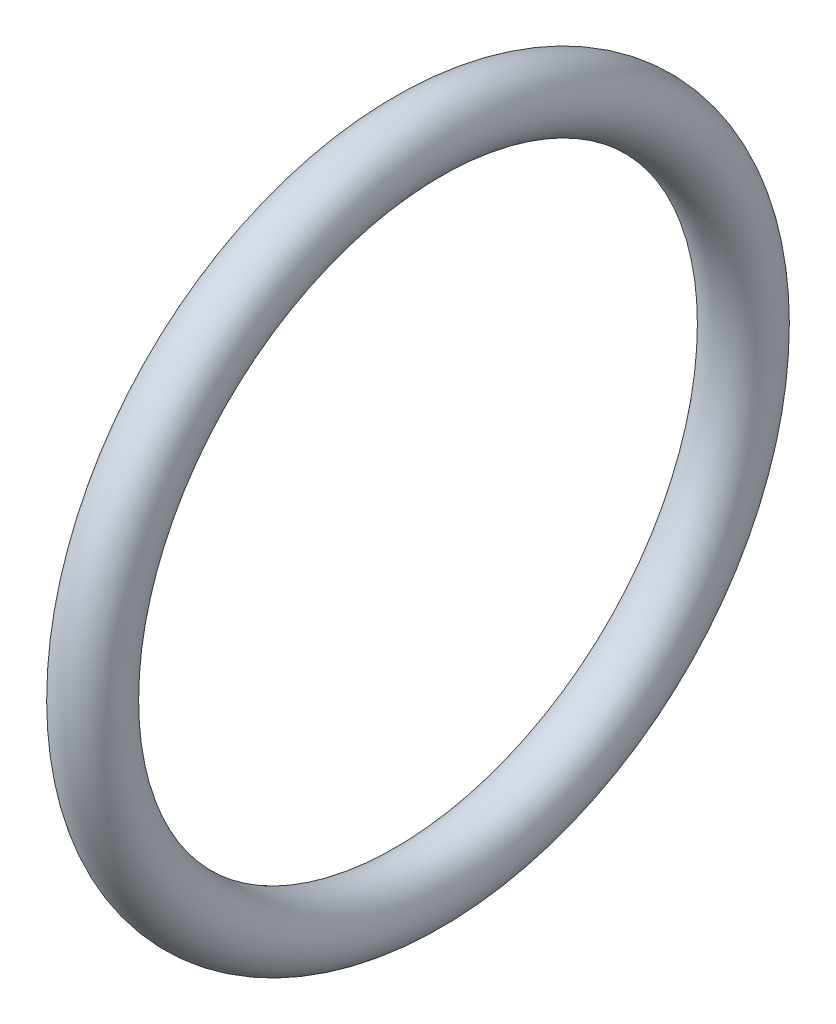
SolidWorks part; units mm, degrees
ref_plane "Plano frontal" through (0, 0, 0) normal (0, 0, 1) x (1, 0, 0)
ref_plane "Plano superior" through (0, 0, 0) normal (0, 1, 0) x (1, 0, 0)
ref_plane "Plano direito" through (0, 0, 0) normal (1, 0, 0) x (0, 0, -1)
sketch "Esboço1" plane through (0, 0, 0) normal (0, 0, 1) x (1, 0, 0)
  line L0 (0, 0) -> (0, 12) construction
  line L1 (0, 0) -> (2.0406, 0) construction
  circle A0 centre (0, 12) radius 1.2
  dimension "D1" = 2.4
  dimension "D2" = 12
revolve "Revolução1" add sketch "Esboço1" angle 360 about L1 other way angle 360
ref_axis "Eixo1" through (-1.32, 0, 0) along (1, 0, 0)
